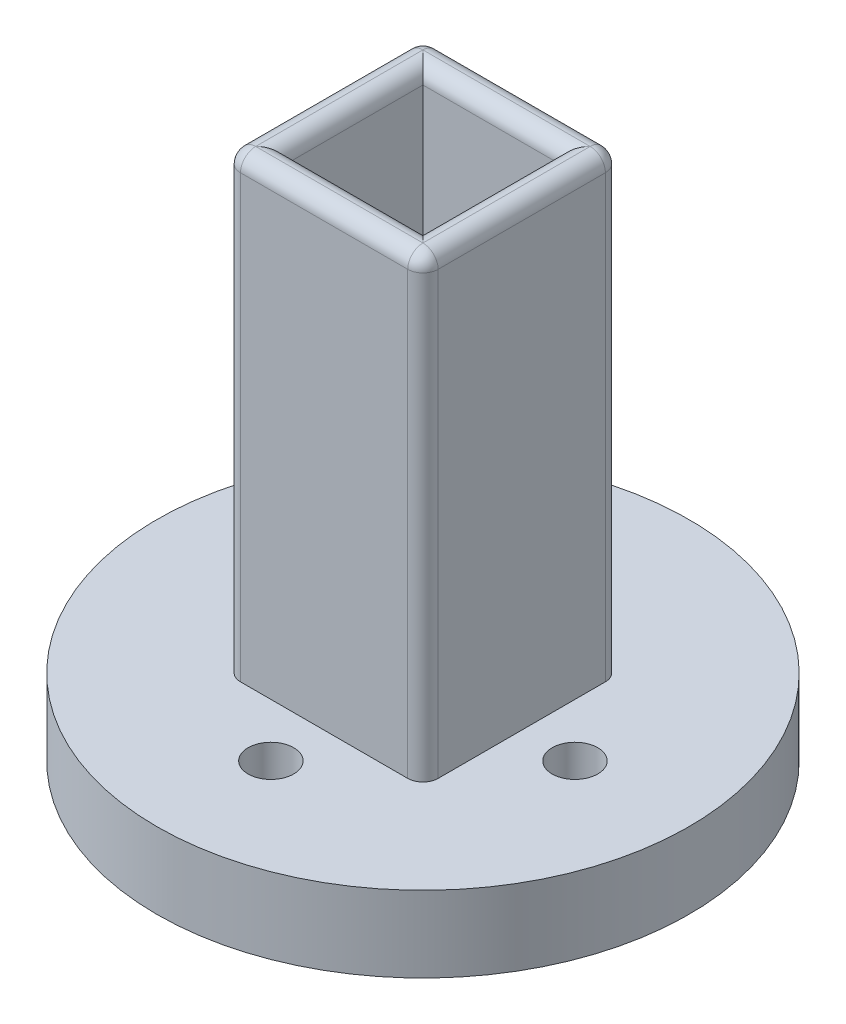
SolidWorks part; units mm, degrees
ref_plane "前视基准面" through (0, 0, 0) normal (0, 0, 1) x (1, 0, 0)
ref_plane "上视基准面" through (0, 0, 0) normal (0, 1, 0) x (1, 0, 0)
ref_plane "右视基准面" through (0, 0, 0) normal (1, 0, 0) x (0, 0, -1)
sketch "草图1" plane through (0, 0, 0) normal (0, 1, 0) x (1, 0, 0)
  circle A0 centre (0, 0) radius 17.5
  circle A1 centre (0, 0) radius 4.05
  circle A3 centre (0, 10) radius 1.5
  circle A4 centre (10, 0) radius 1.5
  circle A5 centre (0, -10) radius 1.5
  circle A6 centre (-10, 0) radius 1.5
  dimension "D1" = 3
  dimension "D2" = 3
  dimension "D3" = 35
  dimension "D4" = 8.1
extrude "凸台-拉伸1" add sketch "草图1" along normal blind 5
sketch "草图2" plane through (0, 5, 0) normal (0, 1, 0) x (1, 0, 0)
  line L1 (-6.5, 6.5) -> (-6.5, -6.5)
  line L2 (-6.5, -6.5) -> (6.5, -6.5)
  line L3 (6.5, -6.5) -> (6.5, 6.5)
  line L4 (6.5, 6.5) -> (-6.5, 6.5)
  line L5 (-4.5, 4.5) -> (4.5, 4.5)
  line L6 (4.5, 4.5) -> (4.5, -4.5)
  line L7 (4.5, -4.5) -> (-4.5, -4.5)
  line L8 (-4.5, -4.5) -> (-4.5, 4.5)
  circle A0 centre (0, 0) radius 4.05 construction
  point P0 (-6.5, 0)
  point P11 (0, 6.5)
  dimension "D1" = 90
  dimension "D2" = 13
  dimension "D3" = 13
  dimension "D4" = 0
  dimension "D5" = 0
  dimension "D6" = 90
  dimension "D7" = 9
  dimension "D8" = 9
extrude "凸台-拉伸2" add sketch "草图2" along normal blind 30
fillet "圆角1" radius 1 12 edges at (4.5, 35, 0) (0, 35, -4.5) (0, 35, 4.5) (-4.5, 35, 0) (-6.5, 35, 0) (0, 35, 6.5) (6.5, 35, 0) (0, 35, -6.5) (-6.5, 20, -6.5) (6.5, 20, -6.5) (6.5, 20, 6.5) (-6.5, 20, 6.5)
